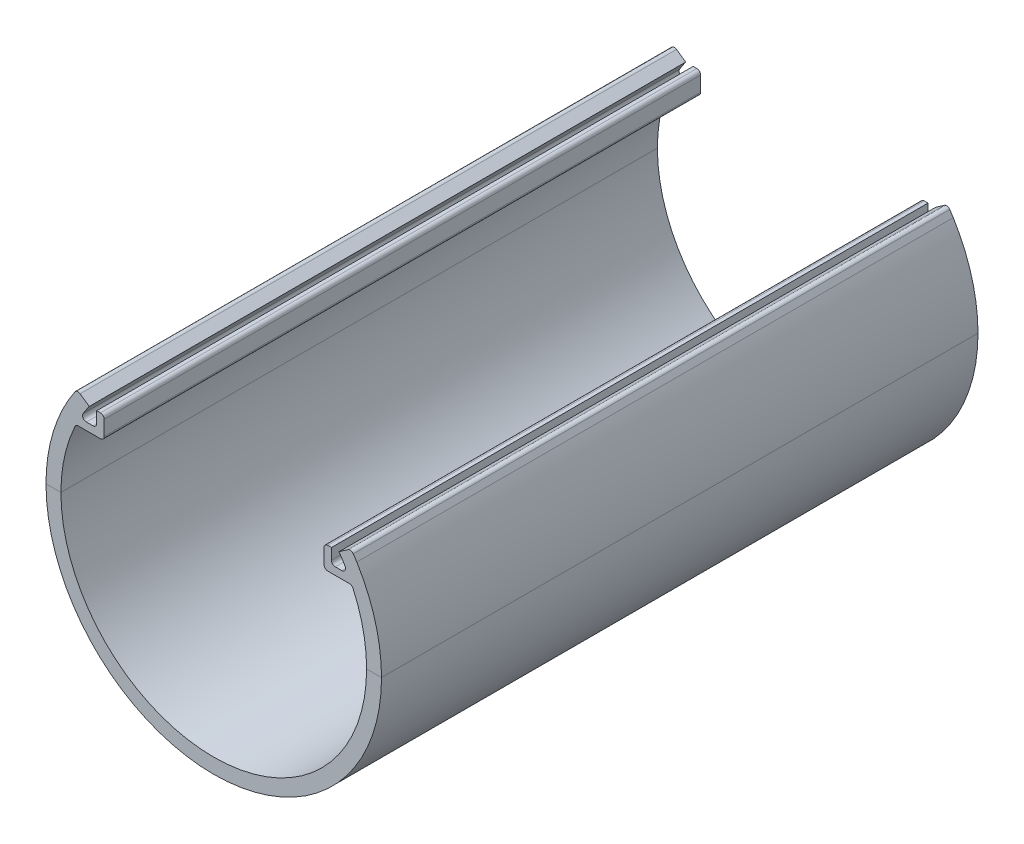
SolidWorks part; units mm, degrees
ref_plane "Front Plane" through (0, 0, 0) normal (0, 0, 1) x (1, 0, 0)
ref_plane "Top Plane" through (0, 0, 0) normal (0, 1, 0) x (1, 0, 0)
ref_plane "Right Plane" through (0, 0, 0) normal (1, 0, 0) x (0, 0, -1)
sketch "Sketch1" plane through (0, 0, 0) normal (0, 0, 1) x (1, 0, 0)
  circle A0 centre (0, 0) radius 22.5
  circle A1 centre (0, 0) radius 20.5
  dimension "D1" = 45
  dimension "D2" = 41
extrude "Boss-Extrude1" add sketch "Sketch1" along normal blind 80
sketch "Sketch2" plane through (0, 0, 80) normal (0, 0, 1) x (1, 0, 0)
  line L1 (-22.5, 0) -> (22.5, 0)
  line L2 (-22.5, 0) -> (-22.5, 22.5)
  line L3 (-22.5, 22.5) -> (22.5, 22.5)
  line L4 (22.5, 0) -> (22.5, 22.5)
  circle A0 centre (0, 0) radius 22.5 construction
extrude "Cut-Extrude1" cut sketch "Sketch2" against normal through all
sketch "Sketch4" plane through (0, 0, 80) normal (0, 0, 1) x (1, 0, 0)
  line L0 (19.1831, 11.7583) -> (18.4309, 12.9055)
  line L1 (16.7926, 11.7583) -> (18.4309, 12.9055)
  line L3 (20.5, 0) -> (22.5, 0)
  line L4 (16.7926, 11.7583) -> (19.1831, 11.7583)
  line L5 (18.4309, 12.9055) -> (16.7926, 11.7583)
  line L6 (15.7926, 11.7583) -> (15.7926, 9.7583)
  line L7 (19.1831, 11.7583) -> (14.7926, 11.7583)
  line L8 (19.1831, 11.7583) -> (19.1831, 8.7583)
  line L9 (19.1831, 8.7583) -> (14.7926, 8.7583)
  line L10 (14.7926, 11.7583) -> (14.7926, 8.7583)
  line L11 (15.7926, 9.7583) -> (18.0285, 9.7583)
  line L12 (16.7926, 11.7583) -> (15.7926, 11.7583)
  line L13 (14.7926, 8.7583) -> (18.5349, 8.7583)
  line L14 (14.7926, 8.7583) -> (14.7926, 11.7583)
  line L15 (14.7926, 11.7583) -> (16.7926, 11.7583)
  line L16 (-16.7023, 11.8863) -> (-18.3406, 13.0335)
  line L17 (-22.5, 0) -> (-20.5, 0) construction
  line L18 (-16.7023, 11.8863) -> (-15.7023, 11.8863)
  line L19 (-19.1041, 11.8863) -> (-14.7023, 11.8863)
  line L20 (-19.1041, 11.8863) -> (-19.1041, 8.8863)
  line L21 (-19.1041, 8.8863) -> (-14.7023, 8.8863)
  line L22 (-14.7023, 11.8863) -> (-14.7023, 8.8863)
  line L23 (-14.7023, 11.8863) -> (-15.7023, 11.8863)
  line L24 (-14.7023, 11.8863) -> (-14.7023, 8.8863)
  line L25 (-14.7023, 8.8863) -> (-15.7023, 8.8863)
  line L26 (-15.7023, 11.8863) -> (-15.7023, 8.8863)
  line L27 (-19.1041, 8.8863) -> (-14.7023, 8.8863)
  line L28 (-19.1041, 8.8863) -> (-19.1041, 9.8863)
  line L29 (-19.1041, 9.8863) -> (-14.7023, 9.8863)
  line L30 (-14.7023, 8.8863) -> (-14.7023, 9.8863)
  line L31 (-15.7023, 11.8863) -> (-15.7023, 9.8863)
  line L32 (-15.7023, 9.8863) -> (-17.9586, 9.8863)
  line L33 (-16.7023, 11.8863) -> (-15.7023, 11.1746)
  line L34 (-15.7023, 11.1746) -> (-15.7023, 9.8863)
  line L35 (-15.7023, 9.8863) -> (-17.9586, 9.8863)
  line L36 (-16.7023, 11.8863) -> (-19.1041, 11.8863)
  line L37 (-19.1041, 11.8863) -> (-19.1041, 8.8863)
  line L38 (-19.1041, 8.8863) -> (-18.4739, 8.8863)
  line L39 (-22.5, 0) -> (-20.5, 0)
  line L40 (-16.7023, 11.8863) -> (-15.7023, 11.8863)
  line L41 (-15.7023, 9.8863) -> (-17.9586, 9.8863)
  arc A0 (22.5, 0) -> (18.4309, 12.9055) centre (0, 0) ccw
  arc A1 (20.5, 0) -> (16.7926, 11.7583) centre (0, 0) ccw
  arc A2 (18.0285, 9.7583) -> (16.7926, 11.7583) centre (0, 0) ccw
  arc A3 (18.5349, 8.7583) -> (16.7926, 11.7583) centre (0, 0) ccw
  arc A4 (-22.5, 0) -> (-18.3406, 13.0335) centre (0, 0) cw
  arc A5 (-20.5, 0) -> (-16.7023, 11.8863) centre (0, 0) cw
  arc A6 (-17.9586, 9.8863) -> (-16.7023, 11.8863) centre (0, 0) cw
  arc A7 (-18.4739, 8.8863) -> (-16.7023, 11.8863) centre (0, 0) cw
  arc A8 (-17.9586, 9.8863) -> (-16.7023, 11.8863) centre (0, 0) cw
  line M11 (22.5, 0) -> (20.5, 0)
  dimension "D1" = 35
  dimension "D7" = 35
  dimension "D2" = 2
  dimension "D3" = 3
  dimension "D4" = 2
  dimension "D5" = 1
  dimension "D6" = 1
  dimension "D8" = 3
  dimension "D9" = 1
  dimension "D10" = 1
  dimension "D11" = 1
extrude "Boss-Extrude2" add sketch "Sketch4" against normal up to surface (80 mm away) separate body contours A1 A0 L8 L9 M11 | L1 L4 L0 | A1 L9 L8 L4 | L9 A1 L11 L6 L7 L10 | L16 A4 L39 A5 | L28 L27 L30 L29 | L24 L23 L26 L25 region at (18.1356, 12.1407, 80) region at (18.3654, 10.5555, 80) region at (20.7342, 5.0849, 80) region at (15.7447, 10.7583, 80) up to face at (0, -10.75, 0)
fillet "Fillet1" radius 0.5 6 edges at (-14.7023, 11.8863, 40) (-18.3406, 13.0335, 40) (-15.7023, 9.8863, 40) (-17.9586, 9.8863, 40) (-18.4739, 8.8863, 40) (-14.7023, 8.8863, 40)
fillet "Fillet2" radius 0.5 6 edges at (18.4309, 12.9055, 40) (18.0285, 9.7583, 40) (15.7926, 9.7583, 40) (14.7926, 11.7583, 40) (14.7926, 8.7583, 40) (18.5349, 8.7583, 40)
